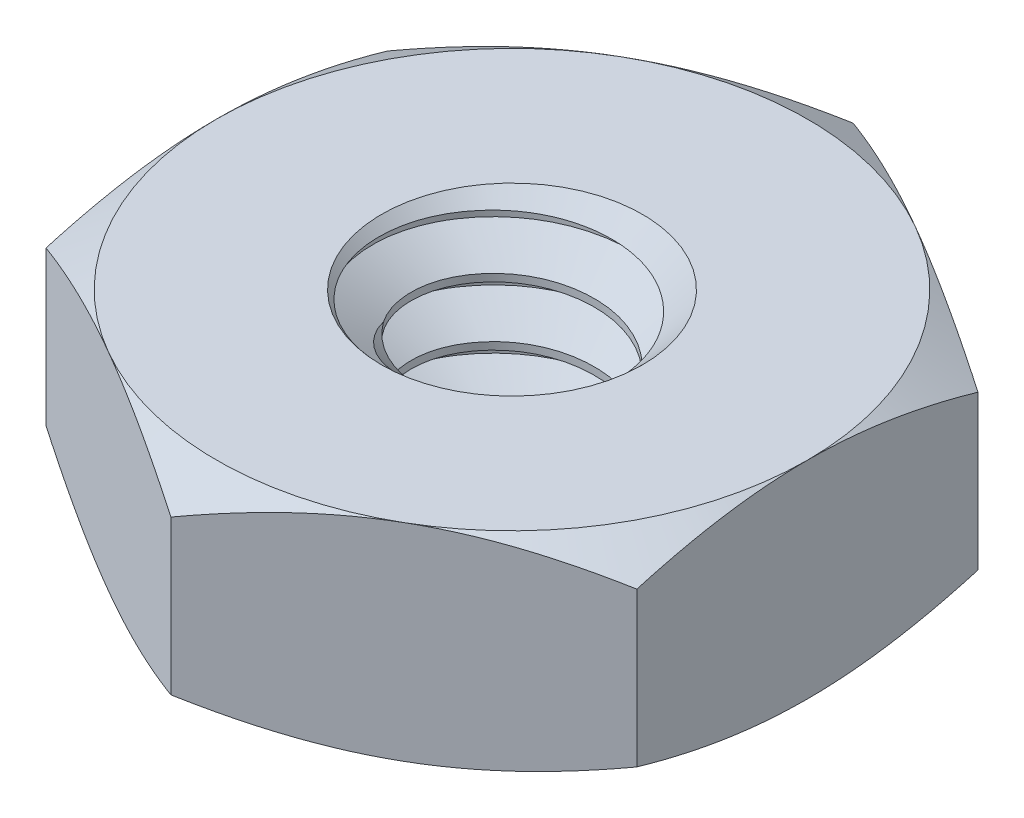
SolidWorks part; units mm, degrees
ref_plane "Front Plane" through (0, 0, 0) normal (0, 0, 1) x (1, 0, 0)
ref_plane "Top Plane" through (0, 0, 0) normal (0, 1, 0) x (1, 0, 0)
ref_plane "Right Plane" through (0, 0, 0) normal (1, 0, 0) x (0, 0, -1)
sketch "Sketch1" plane through (0, 0, 0) normal (0, 1, 0) x (1, 0, 0)
  line L0 (-3.9688, 0) -> (3.9688, 0) construction
  point P0 (0, 0)
  dimension "Width" = 7.9375
sketch "Sketch2" plane through (0, 0, 0) normal (1, 0, 0) x (0, 0, -1)
  line L0 (0, 1.3891) -> (0, -1.3891) construction
  line L1 (-1.7526, 1.3891) -> (1.7526, 1.3891) construction
  line L2 (-1.7526, 1.3891) -> (-1.7526, 0.5953) construction
  point P4 (0, 0)
  point P8 (0, 1.3891)
sketch "Sketch11" plane through (0, 0, 0) normal (0, 1, 0) x (1, 0, 0)
  line L1 (-3.9688, 2.2914) -> (-3.9688, -2.2914)
  line L2 (-3.9688, -2.2914) -> (0, -4.5827)
  line L3 (0, -4.5827) -> (3.9688, -2.2914)
  line L4 (3.9688, -2.2914) -> (3.9688, 2.2914)
  line L5 (3.9688, 2.2914) -> (0, 4.5827)
  line L6 (0, 4.5827) -> (-3.9688, 2.2914)
  circle A0 centre (0, 0) radius 3.9688 construction
  circle A1 centre (0, 0) radius 1.7526
extrude "Boss-Extrude1" add sketch "Sketch11" along normal mid plane 2.7781
sketch "Sketch5" plane through (0, 1.3891, 0) normal (0, 1, 0) x (1, 0, 0)
  circle A0 centre (0, 0) radius 3.9688 construction
  circle A1 centre (0, 0) radius 3.9688
extrude "Cut-Extrude1" cut sketch "Sketch5" against normal through all draft 60 flip side to cut
mirror "Mirror1" about plane through (0, 0, 0) normal (0, 1, 0) of "Cut-Extrude1"
sketch "Sketch27" plane through (0, 0, 0) normal (0, 1, 0) x (1, 0, 0)
  line L0 (1.2393, -1.2393) -> (-1.2393, 1.2393) construction
  line L2 (0, -1.7526) -> (0, 1.7526) construction
  point P5 (0, 0)
  point P8 (1.2393, -1.2393)
  point P9 (-1.2393, 1.2393)
  dimension "D1" = 45
sketch "Sketch22" plane through (0, 1.3891, 0) normal (0, 1, 0) x (1, 0, 0)
  circle A0 centre (0, 0) radius 1.7526 construction
  circle A1 centre (0, 0) radius 1.7526
curve "Helix/Spiral1" pitch 0.7937 height 3.5719 radius 1.7526 centre (0, 1.3891, 0) axis (0, -1, 0) start towards (0, 0, 1) parameters "Pitch"=0.7937
sketch "Sketch23" plane through (0, 1.3891, 0) normal (0, 1, 0) x (1, 0, 0)
  circle A0 centre (0, 0) radius 1.7526
extrude "Boss-Extrude2" add sketch "Sketch23" against normal up to vertex (2.7781 mm away) separate body up to point (0, -1.3891, 0)
sketch "Sketch24" plane through (0, 1.3891, 0) normal (0, 1, 0) x (1, 0, 0)
  line L0 (0, -1.7526) -> (0, 1.7526) construction
  circle A0 centre (0, 0) radius 1.7526
extrude "Boss-Extrude3" add sketch "Sketch24" against normal up to vertex (2.7781 mm away) up to point (0, -1.3891, 0)
sketch "Sketch25" plane through (0, 0, 0) normal (1, 0, 0) x (0, 0, -1)
  line L0 (-1.7526, 1.3891) -> (-1.7526, 2.0836)
  line L1 (-1.7526, 2.0836) -> (-1.237, 1.7859)
  line L2 (-1.237, 1.7859) -> (-1.237, 1.6867)
  line L3 (-1.237, 1.6867) -> (-1.7526, 1.3891)
  line L4 (-1.7526, 1.7363) -> (-1.237, 1.7363) construction
  line L5 (-1.4948, 1.5379) -> (-1.4948, 1.9348) construction
  dimension "D1" = 0.0992
  dimension "D2" = 0.3969
  dimension "D3" = 60
sweep "Cut-Sweep1" cut profiles "Sketch25" path "Helix/Spiral1" align with end faces yes
combine bodies "Combine1" operation type subtract main body 107 bodies to subtract 108
sketch "Sketch26" plane through (0, 1.3891, 0) normal (0, 1, 0) x (1, 0, 0)
  line L0 (-3.9688, 0) -> (3.9688, 0) construction
  circle A0 centre (0, 0) radius 1.7526
extrude "Cut-Extrude2" cut sketch "Sketch26" against normal through all draft 45
mirror "Mirror2" about plane through (0, 0, 0) normal (0, 1, 0) of "Cut-Extrude2"
equation "\"D3@Helix/Spiral1\" = \"Height@Sketch2\" + \"Pitch@Sketch2\""
equation "\"Pitch@Helix/Spiral1\"=\"Pitch@Sketch2\""
equation "\"D1@Sketch25\"=\"Pitch@Sketch2\"*.125"
equation "\"D2@Sketch25\"=\"Pitch@Sketch2\"*.5"
